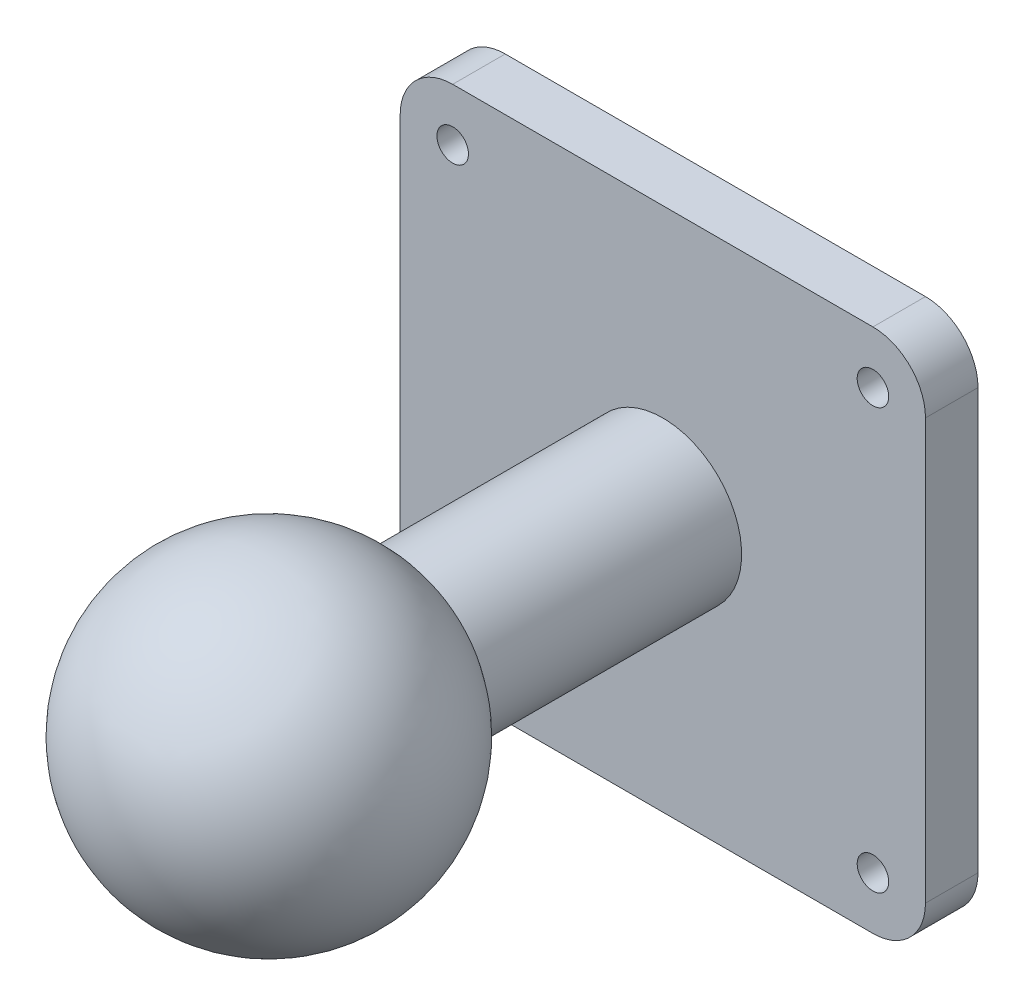
SolidWorks part; units mm, degrees
ref_plane "Alzado" through (0, 0, 0) normal (0, 0, 1) x (1, 0, 0)
ref_plane "Planta" through (0, 0, 0) normal (0, 1, 0) x (1, 0, 0)
ref_plane "Vista lateral" through (0, 0, 0) normal (1, 0, 0) x (0, 0, -1)
sketch "Croquis1" plane through (0, 0, 0) normal (0, 0, 1) x (1, 0, 0)
  line L1 (-25, -25) -> (25, -25)
  line L2 (-25, -25) -> (-25, 25)
  line L3 (-25, 25) -> (25, 25)
  line L4 (25, -25) -> (25, 25)
  line L5 (-25, -25) -> (25, 25) construction
  line L6 (-25, 25) -> (25, -25) construction
  point P0 (0, 0)
  dimension "D1" = 50
  dimension "D2" = 50
extrude "Saliente-Extruir1" add sketch "Croquis1" along normal blind 5
sketch "Croquis2" plane through (0, 0, 5) normal (0, 0, 1) x (1, 0, 0)
  circle A0 centre (0, 0) radius 7.5
  dimension "D1" = 15
ref_plane "Plano1" through (0, 0, 42.5) normal (0, 0, 1) x (1, 0, 0)
sketch "Croquis3" plane through (0, 0, 42.5) normal (0, 0, 1) x (1, 0, 0)
  line L0 (0, 15) -> (0, -15) construction
  line L1 (0, 15) -> (0, -15)
  arc A0 (0, -15) -> (0, 15) centre (0, 0) ccw
  dimension "D1" = 30
revolve "Revolución1" add sketch "Croquis3" angle 360 about L0
extrude "Saliente-Extruir2" add sketch "Croquis2" along normal up to surface (24.5096 mm away) contours A0
sketch "Croquis4" plane through (0, 0, 5) normal (0, 0, 1) x (1, 0, 0)
  line L0 (0, 25) -> (0, 0) construction
  line L1 (25, 25) -> (-25, 25) construction
  line L2 (0, 0) -> (25, 0) construction
  line L3 (25, -25) -> (25, 25) construction
  line L4 (-25, 25) -> (-25, -25) construction
  circle A0 centre (-20, 20) radius 1.5
  circle A1 centre (20, 20) radius 1.5
  circle A2 centre (20, -20) radius 1.5
  circle A3 centre (-20, -20) radius 1.5
  point P12 (-25.9096, 22.2638)
  dimension "D1" = 3
  dimension "D3" = 5
  dimension "D2" = 5
extrude "Cortar-Extruir1" cut sketch "Croquis4" against normal blind 5
fillet "Redondeo1" radius 5 4 edges at (25, -25, 2.5) (25, 25, 2.5) (-25, 25, 2.5) (-25, -25, 2.5)
